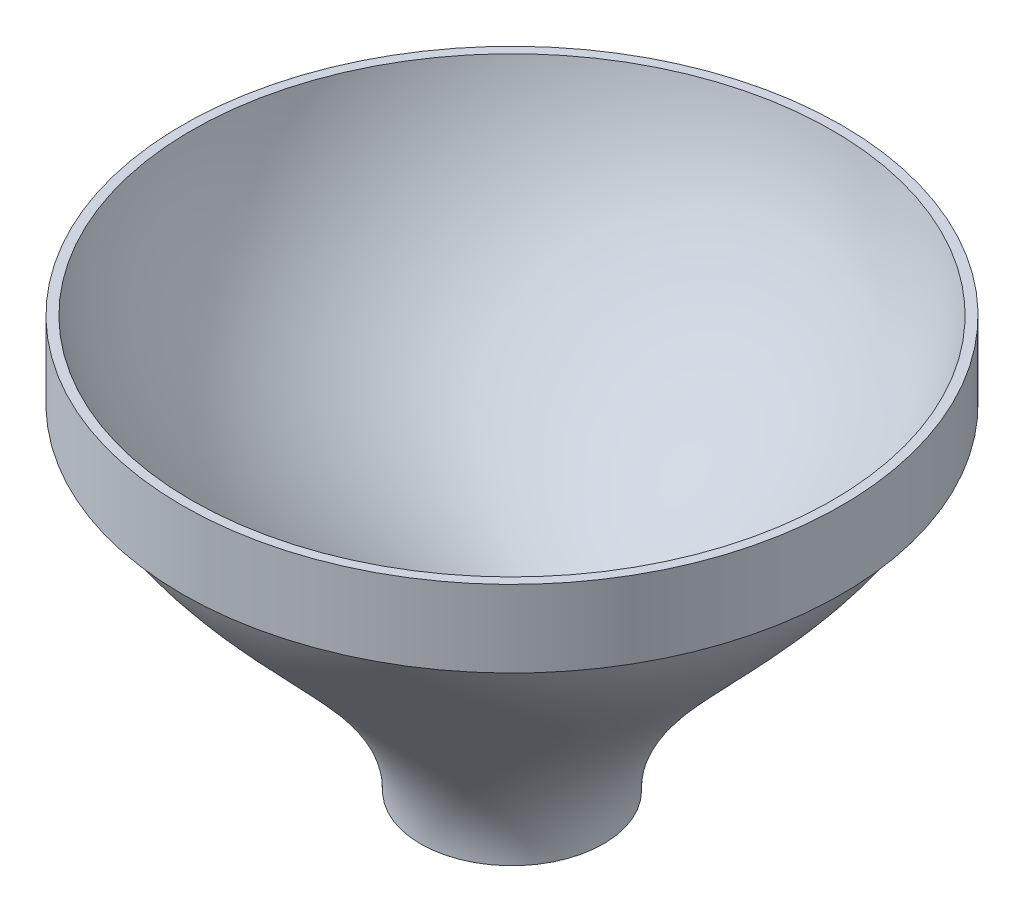
SolidWorks part; units mm, degrees
ref_plane "Płaszczyzna przednia" through (0, 0, 0) normal (0, 0, 1) x (1, 0, 0)
ref_plane "Płaszczyzna górna" through (0, 0, 0) normal (0, 1, 0) x (1, 0, 0)
ref_plane "Płaszczyzna prawa" through (0, 0, 0) normal (1, 0, 0) x (0, 0, -1)
sketch "Sketch1" plane through (0, 0, 0) normal (0, 0, 1) x (1, 0, 0)
  line L15 (24.8342, 148.4714) -> (24.8342, -40.5547) construction
  line L26 (18.8342, 99.8755) -> (16.8342, 99.8755)
  line L30 (-3.1658, 129.1655) -> (-3.9658, 129.1655)
  line L32 (-3.1658, 135.8755) -> (-3.9658, 135.8755)
  line L33 (-3.9658, 135.8755) -> (-3.9658, 129.1655)
  spline S0 degree 3 poles (-3.1658, 135.8755) (0.4907, 117.3938) (18.1254, 113.9802) (18.8342, 99.8755) knots 0 0 0 0 1 1 1 1
  spline S1 degree 3 poles (-3.1658, 129.1655) (1.3725, 118.8356) (17.0932, 110.0443) (16.8342, 99.8755) knots 0 0 0 0 1 1 1 1
  dimension "D7" = 6
  dimension "D1" = 6.71
  dimension "D2" = 0.8
  dimension "D3" = 2
  dimension "D4" = 28
  dimension "D6" = 36
revolve "Revolve1" add sketch "Sketch1" angle 360 about L15 region at (7.0827, 117.3434, 0)
equation "\"outerdiameter\"= 30"
equation "\"wallthick\"= 2"
equation "\"D4@Sketch1\"=\"outerdiameter\"-\"wallthick\""
